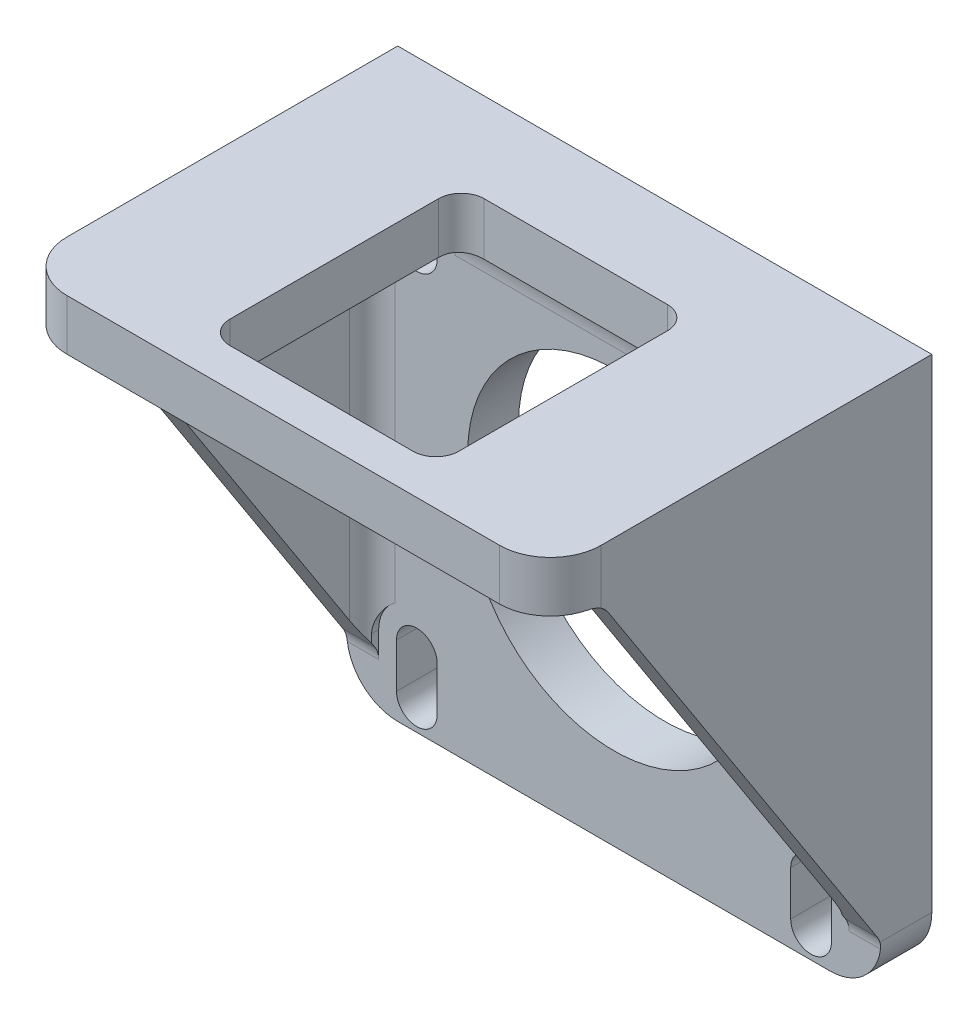
SolidWorks part; units mm, degrees
ref_plane "Front" through (0, 0, 0) normal (0, 0, 1) x (1, 0, 0)
ref_plane "Top" through (0, 0, 0) normal (0, 1, 0) x (1, 0, 0)
ref_plane "Right" through (0, 0, 0) normal (1, 0, 0) x (0, 0, -1)
sketch "Эскиз1" plane through (0, 0, 0) normal (0, 0, 1) x (1, 0, 0)
  line L0 (-17.1, 15.5) -> (-17.1, 12)
  line L1 (-15.5, -15.5) -> (15.5, -15.5) construction
  line L2 (-15.5, -15.5) -> (-15.5, 15.5) construction
  line L3 (-15.5, 15.5) -> (15.5, 15.5) construction
  line L4 (15.5, -15.5) -> (15.5, 15.5) construction
  line L5 (-15.5, -15.5) -> (15.5, 15.5) construction
  line L6 (-15.5, 15.5) -> (15.5, -15.5) construction
  line L7 (-21, -21) -> (21, -21)
  line L8 (-21, -21) -> (-21, 21)
  line L9 (-21, 21) -> (21, 21)
  line L10 (21, -21) -> (21, 21)
  line L11 (-21, -21) -> (21, 21) construction
  line L12 (-21, 21) -> (21, -21) construction
  line L13 (-13.9, 15.5) -> (-13.9, 12)
  line L14 (13.9, 15.5) -> (13.9, 12)
  line L15 (17.1, 15.5) -> (17.1, 12)
  line L16 (-17.1, -15.5) -> (-17.1, -19)
  line L17 (-13.9, -15.5) -> (-13.9, -19)
  line L18 (13.9, -15.5) -> (13.9, -19)
  line L19 (17.1, -15.5) -> (17.1, -19)
  line L20 (0, 0) -> (0, -3) construction
  line L21 (-11.5, -3) -> (-11.5, 0)
  line L22 (11.5, -3) -> (11.5, 0)
  arc A0 (11.5, 0) -> (-11.5, 0) centre (0, 0) ccw
  arc A1 (-13.9, 15.5) -> (-17.1, 15.5) centre (-15.5, 15.5) ccw
  arc A2 (17.1, 15.5) -> (13.9, 15.5) centre (15.5, 15.5) ccw
  arc A3 (-13.9, -15.5) -> (-17.1, -15.5) centre (-15.5, -15.5) ccw
  arc A4 (17.1, -15.5) -> (13.9, -15.5) centre (15.5, -15.5) ccw
  arc A5 (-17.1, 12) -> (-13.9, 12) centre (-15.5, 12) ccw
  arc A6 (-17.1, -19) -> (-13.9, -19) centre (-15.5, -19) ccw
  arc A7 (13.9, -19) -> (17.1, -19) centre (15.5, -19) ccw
  arc A8 (13.9, 12) -> (17.1, 12) centre (15.5, 12) ccw
  arc A9 (-11.5, -3) -> (11.5, -3) centre (0, -3) ccw
  point P0 (0, 0)
  point P6 (0, 0)
  dimension "D5" = 3.5
  dimension "D1" = 31
  dimension "D2" = 31
  dimension "D3" = 42
  dimension "D4" = 42
  dimension "D6" = 3.5
  dimension "D7" = 3.5
  dimension "D8" = 3.5
  dimension "D9" = 3
extrude "Бобышка-Вытянуть1" add sketch "Эскиз1" along normal blind 4
sketch "Эскиз2" plane through (0, 0, 0) normal (0, 0, -1) x (-1, 0, 0)
  line L0 (21, 21) -> (21, -21) construction
  line L1 (-21, 17) -> (21, 17)
  line L2 (-21, 17) -> (-21, 21)
  line L3 (-21, 21) -> (21, 21)
  line L4 (21, 17) -> (21, 21)
  point P4 (21, 17)
  dimension "D1" = 4
extrude "Бобышка-Вытянуть2" add sketch "Эскиз2" against normal blind 30
sketch "Эскиз3" plane through (0, 17, 0) normal (0, -1, 0) x (1, 0, 0)
  line L0 (0, 30) -> (0, 17) construction
  line L1 (-9, 7) -> (9, 7)
  line L2 (-9, 7) -> (-9, 27)
  line L3 (-9, 27) -> (9, 27)
  line L4 (9, 7) -> (9, 27)
  line L5 (-9, 7) -> (9, 27) construction
  line L6 (-9, 27) -> (9, 7) construction
  line L7 (21, 30) -> (-21, 30) construction
  line L8 (0, 17) -> (-21, 17) construction
  line L9 (-21, 30) -> (-21, 4) construction
  point P0 (0, 17)
  dimension "D1" = 20
  dimension "D2" = 18
extrude "Вырез-Вытянуть1" cut sketch "Эскиз3" against normal up to next contours L2 L3 L4 L1
fillet "Скругление1" radius 4 4 edges at (21, -21, 2) (-21, -21, 2) (21, 19, 30) (-21, 19, 30)
sketch "Эскиз6" plane through (0, 0, 4) normal (0, 0, 1) x (1, 0, 0)
  line L0 (-18.5, 15.5) -> (-18.5, 12)
  line L1 (-12.5, 15.5) -> (-12.5, 12)
  line L2 (12.5, 15.5) -> (12.5, 12)
  line L3 (18.5, 15.5) -> (18.5, 12)
  arc A0 (-12.5, 15.5) -> (-18.5, 15.5) centre (-15.5, 15.5) ccw
  arc A1 (18.5, 15.5) -> (12.5, 15.5) centre (15.5, 15.5) ccw
  arc A2 (-18.5, 12) -> (-12.5, 12) centre (-15.5, 12) ccw
  arc A3 (12.5, 12) -> (18.5, 12) centre (15.5, 12) ccw
fillet "Скругление3" radius 4 3 edges at (18.5284, 17, 4) (-18.5284, 17, 4) (0, 17, 4)
sketch "Эскиз7" plane through (-21, 0, 0) normal (-1, 0, 0) x (0, 0, 1)
  line L0 (26, 17) -> (4, 17)
  line L1 (4, 17) -> (4, -17)
  line L2 (4, -17) -> (26, 17)
extrude "Бобышка-Вытянуть3" add sketch "Эскиз7" against normal blind 2
sketch "Эскиз8" plane through (21, 0, 0) normal (1, 0, 0) x (0, 0, -1)
  line L0 (-26, 17) -> (-4, 17)
  line L1 (-4, 17) -> (-4, -17)
  line L2 (-4, -17) -> (-26, 17)
extrude "Бобышка-Вытянуть4" add sketch "Эскиз8" against normal blind 2
fillet "Скругление4" radius 1.8 14 edges at (19, -2, 4) (19, 15.8284, 5.1716) (-19, -2, 4) (-19, 15.8284, 5.1716) (20, -17, 4) (-20, -17, 4) (-20, 17, 26) (20, 17, 26) (19, 17, 17) (-19, 17, 17) (-9, 19, 27) (9, 19, 27) (9, 18.9365, 7) (-9, 18.9365, 7)
sketch "Эскиз9" plane through (0, 0, 0) normal (0, 0, -1) x (-1, 0, 0)
  circle A0 centre (-15.5, 15.5) radius 1.55
  circle A1 centre (15.5, 15.5) radius 1.55
extrude "Вырез-Вытянуть4" cut sketch "Эскиз9" against normal blind 4
sketch "Эскиз10" plane through (0, 0, 4) normal (0, 0, 1) x (1, 0, 0)
  line L0 (-18.5, -15.5) -> (-18.5, -19)
  line L1 (-12.5, -15.5) -> (-12.5, -19)
  line L2 (12.5, -15.5) -> (12.5, -19)
  line L3 (18.5, -15.5) -> (18.5, -19)
  arc A0 (-12.5, -15.5) -> (-18.5, -15.5) centre (-15.5, -15.5) ccw
  arc A1 (18.5, -15.5) -> (12.5, -15.5) centre (15.5, -15.5) ccw
  arc A2 (-18.5, -19) -> (-12.5, -19) centre (-15.5, -19) ccw
  arc A3 (12.5, -19) -> (18.5, -19) centre (15.5, -19) ccw
extrude "Вырез-Вытянуть5" cut sketch "Эскиз10" along normal up to next
extrude "Вырез-Вытянуть6" cut sketch "Эскиз6" along normal blind 8
chamfer "Фаска1" distance 1 angle 45 4 edges at (17.7649, 16.9091, 12) (15.051, 17, 12) (-17.7649, 16.9091, 12) (-15.051, 17, 12)
